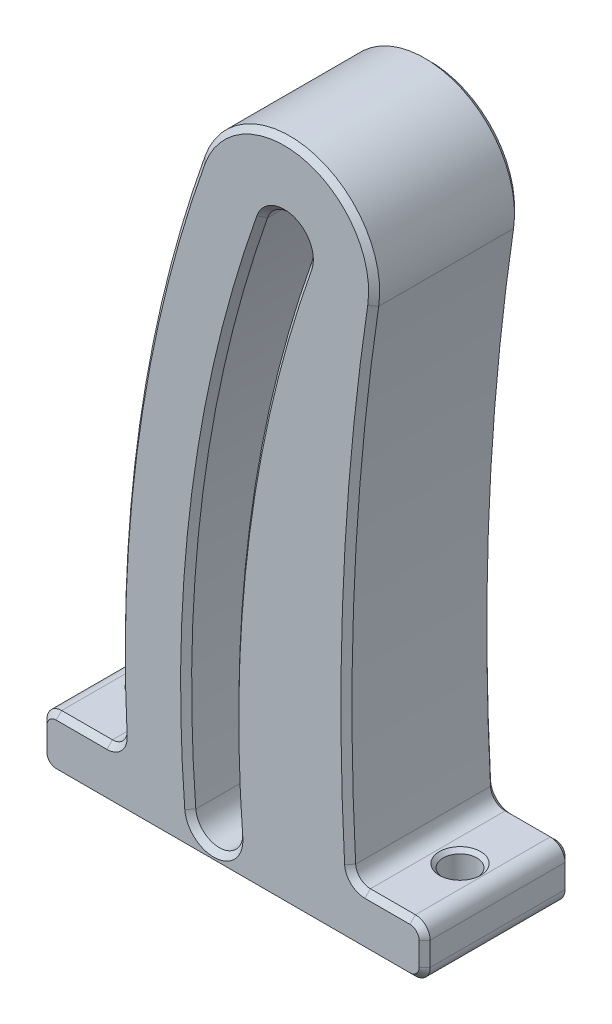
SolidWorks part; units mm, degrees
ref_plane "Front" through (0, 0, 0) normal (0, 0, 1) x (1, 0, 0)
ref_plane "Top" through (0, 0, 0) normal (0, 1, 0) x (1, 0, 0)
ref_plane "Right" through (0, 0, 0) normal (1, 0, 0) x (0, 0, -1)
sketch "Skizze2" plane through (0, 0, 0) normal (0, 0, 1) x (1, 0, 0)
  line L0 (95.5, 79) -> (95.5, 65) construction
  line L4 (106.5523, 7.2) -> (116.5523, 7.2)
  line L5 (116.5523, 7.2) -> (116.5523, 0)
  line L6 (116.5523, 0) -> (64.5523, 0)
  line L8 (64.5523, 0) -> (64.5523, 7.2)
  line L9 (64.5523, 7.2) -> (75.5523, 7.2)
  arc A0 (95.5, 72) -> (87.8331, 6.3984) centre (264.5, 19) ccw construction
  arc A1 (95.5, 72) -> (97.5, 78) centre (264.5, 19) cw construction
  arc A2 (97.5, 78) -> (88.4063, 0) centre (264.5, 19) ccw construction
  arc A3 (94.4828, 79.066) -> (84.7502, 4.7249) centre (264.5, 19) ccw
  arc A4 (100.5172, 76.934) -> (91.1301, 5.2316) centre (264.5, 19) ccw
  arc A5 (100.5172, 76.934) -> (94.4828, 79.066) centre (97.5, 78) ccw
  arc A6 (91.6063, 0) -> (91.5878, 0.3433) centre (88.4063, 0) ccw construction
  arc A7 (85.9968, 82.064) -> (109.5665, 76.2) centre (97.5, 78) cw
  arc A8 (85.9968, 82.064) -> (75.5523, 7.2) centre (264.5, 19) ccw
  arc A9 (84.7502, 4.7249) -> (91.1301, 5.2316) centre (87.9401, 4.9782) ccw
  arc A10 (85.2247, -0.3433) -> (91.6063, 0) centre (88.4063, 0) ccw construction
  arc A11 (85.188, 0) -> (85.2247, -0.3433) centre (264.5, 19) ccw construction
  arc A12 (84.7502, 4.7249) -> (85.188, 0) centre (264.5, 19) ccw construction
  arc A13 (91.1301, 5.2316) -> (91.5878, 0.3433) centre (264.5, 19) ccw construction
  arc A14 (91.1301, 5.2316) -> (87.7156, 8.1703) centre (87.9401, 4.9782) ccw construction
  arc A15 (87.7156, 8.1703) -> (84.7502, 4.7249) centre (87.9401, 4.9782) ccw construction
  arc A16 (109.5665, 76.2) -> (106.5523, 7.2) centre (437.2356, 27.3204) ccw
  point P12 (88.5758, 39.5103)
  dimension "D1" = 3.2
  dimension "D2" = 9
  dimension "D5" = 5
  dimension "D6" = 6.4
  dimension "D3" = 6
  dimension "D4" = 7.2
  dimension "D7" = 11
  dimension "D8" = 10
  dimension "D9" = 52
  dimension "D10" = 69
extrude "Aufsatz-Linear austragen1" add sketch "Skizze2" along normal blind 19.8
sketch "Skizze4" plane through (64.5523, 0, 0) normal (-1, 0, 0) x (0, 0, 1)
  line L0 (10, 0) -> (10, -8.7265) construction
  line L1 (19.8, 0) -> (0, 0) construction
  line L2 (0, 7.2) -> (0, 0) construction
  line L3 (6.5, 0) -> (13.5, 0)
  line L4 (13.5, 0) -> (12.75, -0.75)
  line L5 (12.75, -0.75) -> (7.25, -0.75)
  line L6 (6.5, 0) -> (7.25, -0.75)
  point P10 (10, -0.75)
  dimension "D1" = 10
  dimension "D2" = 7
  dimension "D3" = 0.75
  dimension "D4" = 45
extrude "Aufsatz-Linear austragen2" add sketch "Skizze4" against normal up to surface (52 mm away) up to face at (116.5523, 3.6, 9.9)
sketch "Skizze3" plane through (0, 7.2, 0) normal (0, 1, 0) x (1, 0, 0)
  line L0 (70.0523, 0) -> (70.0523, -19.8) construction
  line L1 (75.5523, 0) -> (64.5523, 0) construction
  line L2 (75.5523, -19.8) -> (64.5523, -19.8) construction
  line L3 (111.5523, 0) -> (111.5523, -19.8) construction
  line L4 (116.5523, 0) -> (106.5523, 0) construction
  line L5 (116.5523, -19.8) -> (106.5523, -19.8) construction
  circle A0 centre (70.0523, -10) radius 2.3
  circle A1 centre (111.5523, -10) radius 2.3
  dimension "D1" = 4.6
  dimension "D2" = 10
extrude "Schnitt-Linear austragen1" cut sketch "Skizze3" against normal blind 10
sketch "Skizze5" plane through (0, 0, 0) normal (0, -1, 0) x (1, 0, 0)
  line L0 (70.0523, 14.15) -> (64.5523, 14.15)
  line L1 (70.0523, 5.85) -> (64.5523, 5.85)
  line L2 (64.5523, 5.85) -> (64.5523, 14.15)
  line L3 (90.5523, 19.8) -> (90.5523, 0) construction
  line L4 (64.5523, 19.8) -> (116.5523, 19.8) construction
  line L5 (64.5523, 0) -> (116.5523, 0) construction
  line L6 (64.5523, 19.8) -> (64.5523, 13.5) construction
  line L7 (116.5523, 5.85) -> (116.5523, 14.15)
  line L8 (111.0523, 5.85) -> (116.5523, 5.85)
  line L9 (111.0523, 14.15) -> (116.5523, 14.15)
  arc A0 (70.0523, 5.85) -> (70.0523, 14.15) centre (70.0523, 10) ccw
  arc A1 (70.0523, 14.15) -> (70.0523, 5.85) centre (70.0523, 10) ccw construction
  arc A2 (111.0523, 14.15) -> (111.0523, 5.85) centre (111.0523, 10) cw construction
  arc A3 (111.0523, 5.85) -> (111.0523, 14.15) centre (111.0523, 10) cw
  dimension "D1" = 8.3
extrude "Schnitt-Linear austragen2" cut sketch "Skizze5" along normal blind 10
fillet "Verrundung1" radius 2 6 edges at (64.5523, 0, 9.9) (116.5523, 0, 9.9) (64.5523, 7.2, 9.9) (75.5523, 7.2, 9.9) (106.5523, 7.2, 9.9) (116.5523, 7.2, 9.9)
chamfer "Fase1" distance 0.75 angle 45 36 edges at (100.4455, 89.8391, 19.8) (77.1485, 46.201, 19.8) (106.2991, 42.7244, 19.8) (74.8854, 7.8225, 19.8) (107.065, 7.7474, 19.8) (69.9939, 7.2, 19.8) (111.496, 7.2, 19.8) (65.1381, 6.6142, 19.8) (115.9665, 6.6142, 19.8) (64.5523, 3.6, 19.8) (116.5523, 3.6, 19.8) (65.1381, 0.5858, 19.8) (115.9665, 0.5858, 19.8) (90.5523, 0, 19.8) (90.5523, 0, 0) (64.5523, 3.6, 0) (65.1381, 6.6142, 0) (116.5523, 3.6, 0) (69.9939, 7.2, 0) (115.9665, 6.6142, 0) (74.8854, 7.8225, 0) (111.496, 7.2, 0) (77.1485, 46.201, 0) (107.065, 7.7474, 0) (100.4455, 89.8391, 0) (106.2991, 42.7244, 0) (92.0557, 41.5761, 19.8) (98.566, 81.0172, 19.8) (88.1935, 1.7883, 19.8) (85.7099, 42.4069, 19.8) (92.0557, 41.5761, 0) (98.566, 81.0172, 0) (88.1935, 1.7883, 0) (85.7099, 42.4069, 0) (65.1381, 0.5858, 0) (115.9665, 0.5858, 0)
fillet "Verrundung2" radius 1 2 edges at (106.9023, -0.75, 10) (74.2023, -0.75, 10)
chamfer "Fase2" distance 0.5 angle 45 4 edges at (111.5523, 7.2, 12.3) (111.5523, 0, 12.3) (70.0523, 0, 7.7) (70.0523, 7.2, 12.3)
